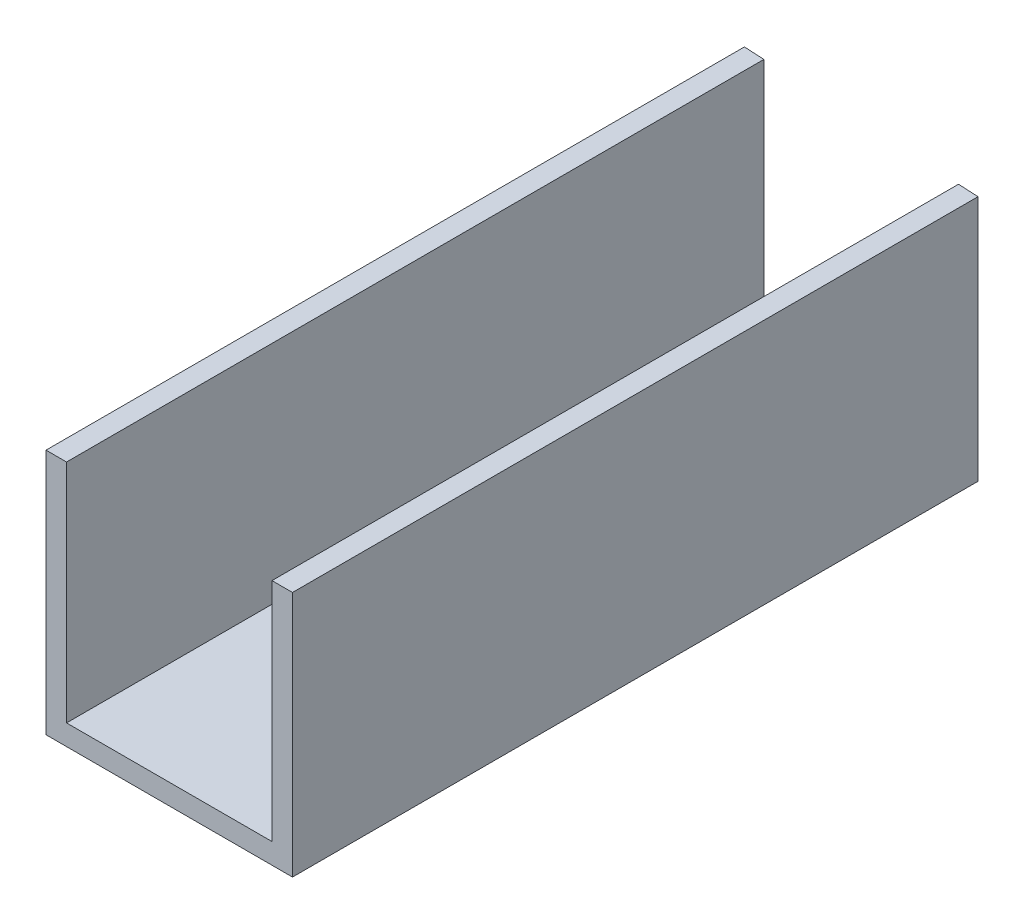
SolidWorks part; units mm, degrees
ref_plane "Front Plane" through (0, 0, 0) normal (0, 0, 1) x (1, 0, 0)
ref_plane "Top Plane" through (0, 0, 0) normal (0, 1, 0) x (1, 0, 0)
ref_plane "Right Plane" through (0, 0, 0) normal (1, 0, 0) x (0, 0, -1)
sketch "Sketch1" plane through (0, 0, 0) normal (0, 0, 1) x (1, 0, 0)
  line L0 (18.3712, 0) -> (-19.7288, 0)
  line L1 (-19.7288, 0) -> (-19.7288, 38.1)
  line L2 (-19.7288, 38.1) -> (-16.5538, 38.1)
  line L3 (-16.5538, 38.1) -> (-16.5538, 3.175)
  line L4 (-16.5538, 3.175) -> (15.1962, 3.175)
  line L5 (15.1962, 3.175) -> (15.1962, 38.1)
  line L6 (15.1962, 38.1) -> (18.3712, 38.1)
  line L7 (18.3712, 38.1) -> (18.3712, 0)
  dimension "D1" = 3.175
  dimension "D2" = 3.175
  dimension "D3" = 3.175
  dimension "D4" = 38.1
  dimension "D5" = 38.1
  dimension "D6" = 38.1
extrude "Boss-Extrude1" add sketch "Sketch1" along normal blind 107.95
sketch "Sketch2" plane through (0, 38.1, 0) normal (0, 1, 0) x (1, 0, 0)
  line L0 (-19.7288, 0) -> (18.3712, 0)
  line L1 (18.3712, 0) -> (18.3712, -1.9967)
  line L2 (18.3712, -107.95) -> (18.3712, 0) construction
  line L3 (18.3712, -1.9967) -> (-19.7288, 0)
  dimension "D1" = 3
extrude "Cut-Extrude1" cut sketch "Sketch2" against normal blind 98.425
